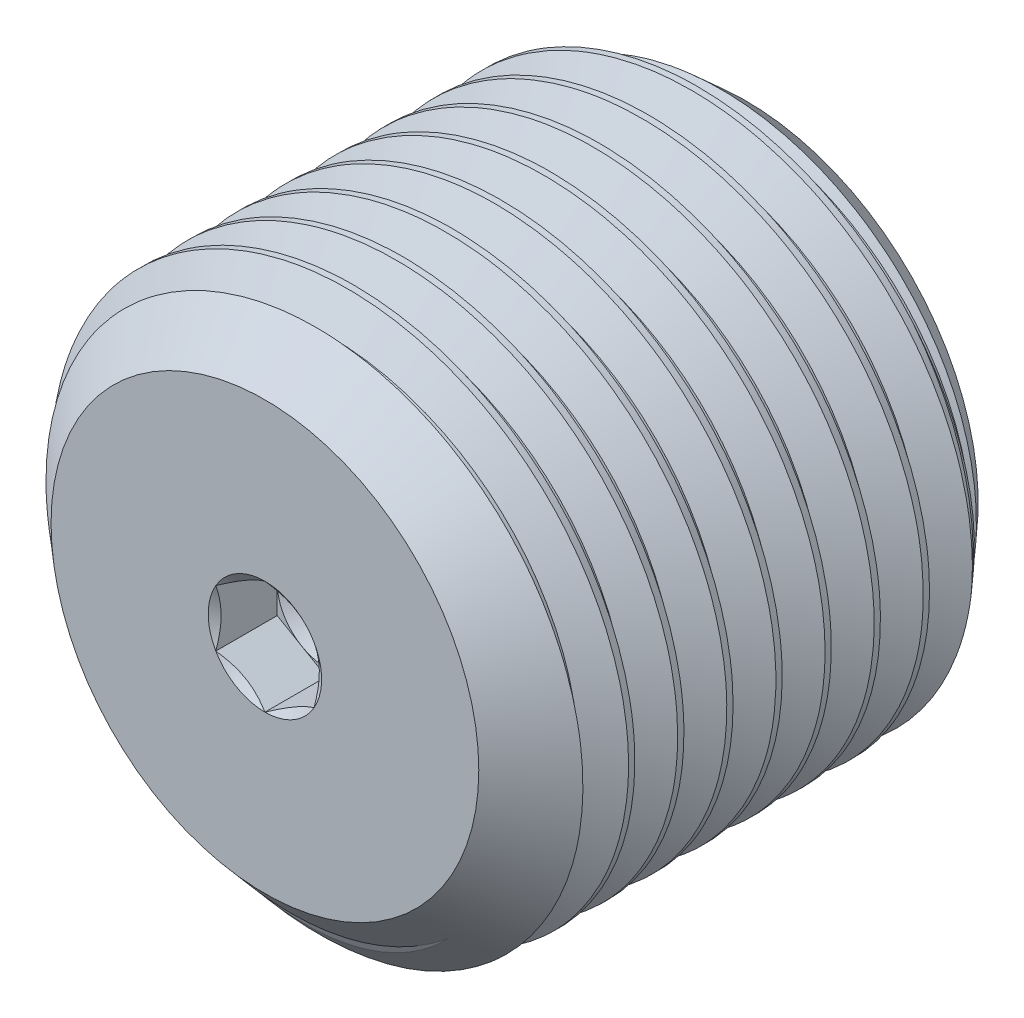
SolidWorks part; units mm, degrees
ref_plane "Front" through (0, 0, 0) normal (0, 0, 1) x (1, 0, 0)
ref_plane "Top" through (0, 0, 0) normal (0, 1, 0) x (1, 0, 0)
ref_plane "Right" through (0, 0, 0) normal (1, 0, 0) x (0, 0, -1)
sketch "Sketch22" plane through (0, 0, 0) normal (1, 0, 0) x (0, 0, -1)
  line L0 (-1.7145, 0) -> (-1.7145, 1.524)
  line L1 (-1.7145, 1.524) -> (-1.3281, 1.9685)
  line L2 (-1.3281, 1.9685) -> (1.3647, 1.9685)
  line L3 (1.3647, 1.9685) -> (1.7145, 1.6535)
  line L4 (0.0183, 1.9685) -> (0.0183, -1.9685) construction
  line L5 (1.7145, 0) -> (-1.7145, 0)
  line L6 (-1.7145, 1.524) -> (-1.7145, -1.524) construction
  line L7 (1.7145, 0) -> (1.7145, 1.6535)
  point P11 (0.0183, 0)
  dimension "Length" = 3.429
  dimension "D3" = 41
  dimension "D6" = 48
  dimension "Dia" = 3.937
  dimension "D1" = 3.048
  dimension "D2" = 0.315
revolve "Revolve1" add sketch "Sketch22" angle 360 about L5
ref_plane "Plane1" through (0, 0, -1.7145) normal (0, 0, 1) x (1, 0, 0)
sketch "Sketch23" plane through (0, 0, 1.7145) normal (0, 0, 1) x (1, 0, 0)
  line L1 (0, 0.4041) -> (-0.35, 0.2021)
  line L2 (-0.35, 0.2021) -> (-0.35, -0.2021)
  line L3 (-0.35, -0.2021) -> (0, -0.4041)
  line L4 (0, -0.4041) -> (0.35, -0.2021)
  line L5 (0.35, -0.2021) -> (0.35, 0.2021)
  line L6 (0.35, 0.2021) -> (0, 0.4041)
  circle A0 centre (0, 0) radius 0.35 construction
  dimension "Hex" = 0.7
extrude "Cut-Extrude10" cut sketch "Sketch23" against normal blind 0.4375
sketch "Sketch24" plane through (0, 0, 1.7145) normal (0, 0, 1) x (1, 0, 0)
  circle A0 centre (0, 0) radius 0.4041
extrude "Cut-Extrude11" cut sketch "Sketch24" against normal through all draft 55
sketch "Sketch26" plane through (0, 0, 1.277) normal (0, 0, 1) x (1, 0, 0)
  circle A0 centre (0, 0) radius 0.35 construction
  circle A1 centre (0, 0) radius 0.35
extrude "Cut-Extrude12" cut sketch "Sketch26" against normal through all draft 60
sketch "Sketch30" plane through (0, 0, 0) normal (1, 0, 0) x (0, 0, -1)
  line L0 (-1.3281, 1.9685) -> (1.3647, 1.9685) construction
  line L1 (-1.7145, 0) -> (-1.7145, 1.524) construction
  line L2 (1.7145, 0) -> (1.7145, 1.6535) construction
  point P0 (-1.7145, 1.9685)
  point P1 (1.7145, 1.9685)
  point P2 (1.7145, -1.9685)
  point P11 (0.8395, -1.9685)
  dimension "D1" = 0.875
sketch "Sketch27" plane through (0, 0, -1.7145) normal (0, 0, 1) x (1, 0, 0)
  circle A0 centre (0, 0) radius 1.9685 construction
  circle A1 centre (0, 0) radius 1.9685
ref_plane "Plane2" through (0, 0, -1.6645) normal (0, 0, -1) x (-1, 0, 0)
sketch "Sketch31" plane through (0, 0, -1.6645) normal (0, 0, -1) x (-1, 0, 0)
  circle A0 centre (0, 0) radius 1.9685 construction
  circle A1 centre (0, 0) radius 1.9685
curve "Helix/Spiral1" pitch 0.35 height 9.779 radius 1.9685 centre (0, 0, -1.6645) axis (0, 0, 1) start towards (0, 1, 0)
sketch "Sketch28" plane through (0, 0, 0) normal (1, 0, 0) x (0, 0, -1)
  line L0 (1.6427, 2.0063) -> (1.9917, 2.0063) construction
  line L1 (1.9917, 2.0063) -> (1.839, 1.7418) construction
  line L2 (1.839, 1.7418) -> (1.7954, 1.7418)
  line L3 (1.7954, 1.7418) -> (1.6427, 2.0063) construction
  line L4 (1.8172, 2.0063) -> (1.8172, 1.9685) construction
  line L5 (1.8172, 1.7418) -> (1.8172, 1.704) construction
  line L6 (1.6536, 1.9874) -> (1.9808, 1.9874)
  line L7 (1.9917, 2.0063) -> (1.8172, 1.704) construction
  line L8 (1.6427, 2.0063) -> (1.8172, 1.704) construction
  line L9 (1.6427, 2.0063) -> (1.7954, 1.7418) construction
  line L10 (1.9917, 2.0063) -> (1.839, 1.7418) construction
  line L11 (1.6645, 1.9685) -> (1.9699, 1.9685) construction
  line L12 (1.9808, 1.9874) -> (1.839, 1.7418)
  line L13 (1.6536, 1.9874) -> (1.7954, 1.7418)
  line L15 (1.6645, -1.9685) -> (1.6645, 1.9685) construction
  point P10 (1.8172, 1.9685)
  point P11 (1.8172, 1.9874)
  dimension "D3" = 60
  dimension "D1" = 0.349
  dimension "D2" = 0.0436
sweep "Cut-Sweep1" cut profiles "Sketch28" path "Helix/Spiral1"
ref_plane "Contact Plane 1" through (0, 0, 1.7145) normal (0, 0, 1) x (1, 0, 0)
ref_plane "Contact Plane 2" through (0, 0, -1.7145) normal (0, 0, -1) x (-1, 0, 0)
ref_axis "Center Axis 1" through (0, 0, -1.7145) along (0, 0, 1)
equation "\"D3@Helix/Spiral1\"=\"Length@Sketch22\"+.25"
equation "\"D1@Sketch30\" = \"D4@Helix/Spiral1\" * 2.5"
equation "\"hex Depth@Cut-Extrude10\" = \"Hex@Sketch23\" * .625"
equation "\"D2@Sketch22\"=\"D4@Helix/Spiral1\"*.90"
equation "\"D2@Sketch28\"=\"D1@Sketch28\"/8"
